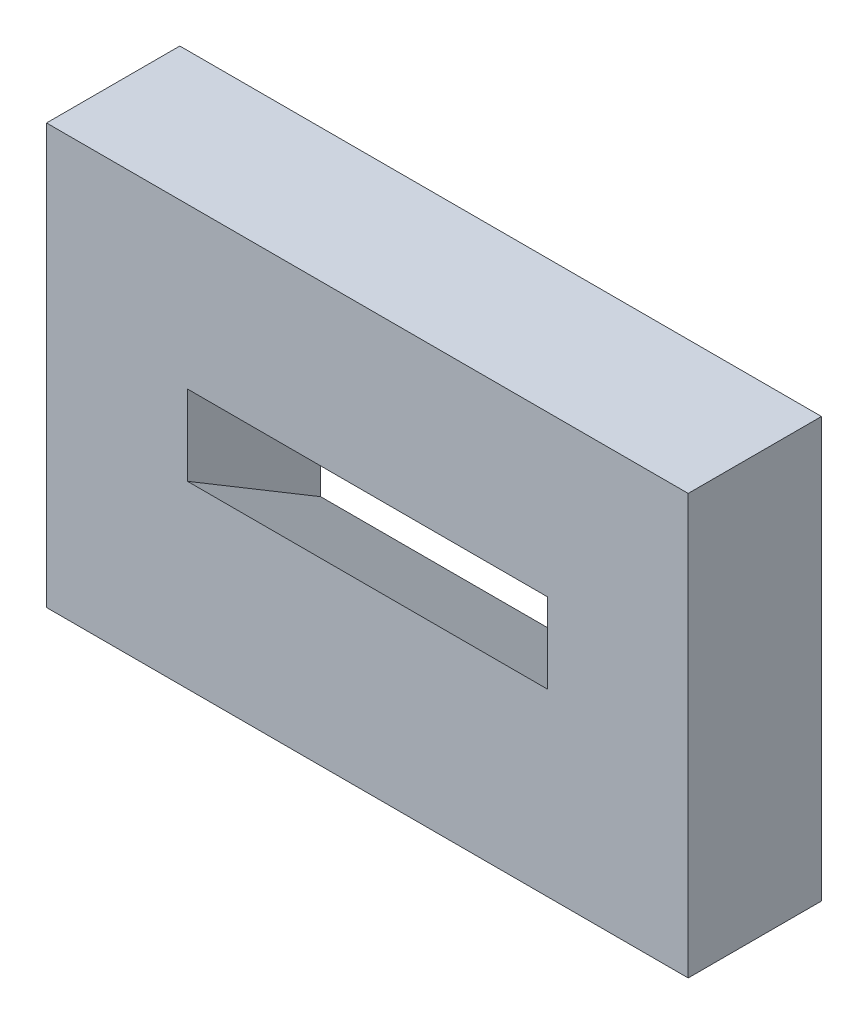
SolidWorks part; units mm, degrees
ref_plane "Ebene vorne" through (0, 0, 0) normal (0, 0, 1) x (1, 0, 0)
ref_plane "Ebene oben" through (0, 0, 0) normal (0, 1, 0) x (1, 0, 0)
ref_plane "Ebene rechts" through (0, 0, 0) normal (1, 0, 0) x (0, 0, -1)
sketch "Skizze1" plane through (0, 0, 0) normal (0, 0, 1) x (1, 0, 0)
  line L1 (-55, -85) -> (55, -85)
  line L2 (-55, -85) -> (-55, 85)
  line L3 (-55, 85) -> (55, 85)
  line L4 (55, -85) -> (55, 85)
  line L5 (-55, -85) -> (55, 85) construction
  line L6 (-55, 85) -> (55, -85) construction
  point P0 (0, 0)
  dimension "D1" = 110
  dimension "D2" = 170
extrude "Aufsatz-Linear austragen1" add sketch "Skizze1" along normal blind 5
sketch "Skizze2" plane through (0, 0, 5) normal (0, 0, 1) x (1, 0, 0)
  line L0 (-55, -85) -> (55, -85) construction
  line L1 (0, 85) -> (0, -85) construction
  line L2 (55, 85) -> (-55, 85) construction
  circle A1 centre (0, 0) radius 27
  dimension "D2" = 54
fillet "Verrundung1" radius 5 4 edges at (-55, -85, 2.5) (55, -85, 2.5) (55, 85, 2.5) (-55, 85, 2.5)
sketch "Skizze3" plane through (0, 0, 5) normal (0, 0, 1) x (1, 0, 0)
  line L0 (-35, 35) -> (-35, 17)
  line L1 (-35, -35) -> (35, -35) construction
  line L2 (-35, -35) -> (-35, 35) construction
  line L3 (-35, 35) -> (35, 35) construction
  line L4 (35, -35) -> (35, 35) construction
  line L5 (-35, -35) -> (35, 35) construction
  line L6 (-35, 35) -> (35, -35) construction
  line L7 (-35, 35) -> (-17, 35)
  line L8 (35, 35) -> (17, 35)
  line L9 (35, 35) -> (35, 17)
  line L10 (35, -35) -> (35, -17)
  line L11 (35, -35) -> (17, -35)
  line L12 (-35, -35) -> (-17, -35)
  line L13 (-35, -35) -> (-35, -17)
  arc A0 (-17, 35) -> (-35, 17) centre (0, 0) ccw
  arc A1 (35, 17) -> (17, 35) centre (0, 0) ccw
  arc A2 (17, -35) -> (35, -17) centre (0, 0) ccw
  arc A3 (-35, -17) -> (-17, -35) centre (0, 0) ccw
  point P0 (0, 0)
  point P21 (0, 0)
  dimension "D2" = 18
  dimension "D1" = 70
  dimension "D3" = 4
extrude "Schnitt-Linear austragen1" cut sketch "Skizze3" against normal through all
extrude "Schnitt-Linear austragen2" cut sketch "Skizze2" against normal blind 3
chamfer "Fase1" distance 3 angle 45 1 edges at (27, 0, 5)
sketch "Skizze4" plane through (0, 0, 0) normal (0, 0, -1) x (-1, 0, 0)
  line L0 (-50, 85) -> (50, 85) construction
  line L1 (-55, -80) -> (-55, 80) construction
  circle A0 centre (-49, 67) radius 4
  dimension "D1" = 18
  dimension "D3" = 8
  dimension "D2" = 6
extrude "Aufsatz-Linear austragen2" add sketch "Skizze4" along normal blind 69
chamfer "Fase2" distance 1 angle 45 1 edges at (45, 67, 0)
ref_plane "Ebene1" through (0, 0, -67) normal (0, 0, -1) x (-1, 0, 0)
sketch "Skizze5" plane through (0, 0, -67) normal (0, 0, -1) x (-1, 0, 0)
  circle A0 centre (-49, 67) radius 3
  circle A1 centre (-49, 67) radius 3.5
  dimension "D1" = 6
  dimension "D2" = 7
extrude "Schnitt-Linear austragen3" [suppressed] cut sketch "Skizze5" against normal blind 1
pattern_linear "Lineares Muster1" count 2 spacing 134 along (0, -1, 0) count 2 spacing 98 along (-1, 0, 0) of "Aufsatz-Linear austragen2", "Fase2"
fillet "Verrundung2" radius 1 12 edges at (-17, 35, 2.5) (-35, 35, 2.5) (-35, 17, 2.5) (-17, -35, 2.5) (-35, -17, 2.5) (-35, -35, 2.5) (35, -35, 2.5) (17, -35, 2.5) (35, -17, 2.5) (35, 17, 2.5) (35, 35, 2.5) (17, 35, 2.5)
thread "Gewinde1" pitch 1 method cut profile "Gewindeprofil1" start angle 0, offset 0, length 12, pitch 1, diameter 8
ref_plane "Ebene2" through (53, 67, -69) normal (0, -1, 0) x (1, 0, 0)
sketch "Gewindeprofil1" plane through (53, 67, -69) normal (0, -1, 0) x (1, 0, 0)
  line L0 (0, 0) -> (0, 1) construction
  line L11 (0, 0) -> (0, 0.875)
  line L12 (0, 0.875) -> (-0.5413, 0.5625)
  line L13 (-0.5413, 0.5625) -> (-0.5413, 0.3125)
  line L15 (-0.5413, 0.3125) -> (0, 0)
  line L17 (-0.5413, 0.4375) -> (0, 0.4375) construction
  point P2 (0, 0)
  dimension "Pitch" = 1
  dimension "Profile_Angle" = 60
  dimension "Profile_Land" = 0.25
  dimension "Profile_Height" = 0.5413
thread "Gewinde2" pitch 1 method cut profile "Gewindeprofil2" start angle 0, offset 0, length 12, pitch 1, diameter 8
ref_plane "Ebene3" through (53, -67, -69) normal (0, -1, 0) x (1, 0, 0)
sketch "Gewindeprofil2" plane through (53, -67, -69) normal (0, -1, 0) x (1, 0, 0)
  line L0 (0, 0) -> (0, 1) construction
  line L11 (0, 0) -> (0, 0.875)
  line L12 (0, 0.875) -> (-0.5413, 0.5625)
  line L13 (-0.5413, 0.5625) -> (-0.5413, 0.3125)
  line L15 (-0.5413, 0.3125) -> (0, 0)
  line L17 (-0.5413, 0.4375) -> (0, 0.4375) construction
  point P2 (0, 0)
  dimension "Pitch" = 1
  dimension "Profile_Angle" = 60
  dimension "Profile_Land" = 0.25
  dimension "Profile_Height" = 0.5413
thread "Gewinde3" pitch 1 method cut profile "Gewindeprofil3" start angle 0, offset 0, length 12, pitch 1, diameter 8
ref_plane "Ebene4" through (-45, -67, -69) normal (0, -1, 0) x (1, 0, 0)
sketch "Gewindeprofil3" plane through (-45, -67, -69) normal (0, -1, 0) x (1, 0, 0)
  line L0 (0, 0) -> (0, 1) construction
  line L11 (0, 0) -> (0, 0.875)
  line L12 (0, 0.875) -> (-0.5413, 0.5625)
  line L13 (-0.5413, 0.5625) -> (-0.5413, 0.3125)
  line L15 (-0.5413, 0.3125) -> (0, 0)
  line L17 (-0.5413, 0.4375) -> (0, 0.4375) construction
  point P2 (0, 0)
  dimension "Pitch" = 1
  dimension "Profile_Angle" = 60
  dimension "Profile_Land" = 0.25
  dimension "Profile_Height" = 0.5413
thread "Gewinde4" pitch 1 method cut profile "Gewindeprofil4" start angle 0, offset 0, length 12, pitch 1, diameter 8
ref_plane "Ebene5" through (-45, 67, -69) normal (0, -1, 0) x (1, 0, 0)
sketch "Gewindeprofil4" plane through (-45, 67, -69) normal (0, -1, 0) x (1, 0, 0)
  line L0 (0, 0) -> (0, 1) construction
  line L11 (0, 0) -> (0, 0.875)
  line L12 (0, 0.875) -> (-0.5413, 0.5625)
  line L13 (-0.5413, 0.5625) -> (-0.5413, 0.3125)
  line L15 (-0.5413, 0.3125) -> (0, 0)
  line L17 (-0.5413, 0.4375) -> (0, 0.4375) construction
  point P2 (0, 0)
  dimension "Pitch" = 1
  dimension "Profile_Angle" = 60
  dimension "Profile_Land" = 0.25
  dimension "Profile_Height" = 0.5413
sketch "Skizze10" plane through (0, 0, -69) normal (0, 0, -1) x (-1, 0, 0)
  line L0 (-49, 72) -> (-49, 62) construction
  line L2 (-60, -75) -> (60, -75)
  line L3 (-60, -75) -> (-60, 75)
  line L4 (-60, 75) -> (60, 75)
  line L5 (60, -75) -> (60, 75)
  line L6 (-60, -75) -> (60, 75) construction
  line L7 (-60, 75) -> (60, -75) construction
  circle A0 centre (-49, 67) radius 5 construction
  point P5 (0, 0)
  dimension "D1" = 150
  dimension "D2" = 120
extrude "Schnitt-Linear austragen4" cut sketch "Skizze10" against normal blind 2
sketch "Skizze12" plane through (0, 0, 0) normal (0, 0, -1) x (-1, 0, 0)
  line L0 (49, 67) -> (52.4587, 67) construction
  line L1 (49, 67) -> (45, 67) construction
  line L2 (49, 67) -> (49, 70.7835) construction
  line L3 (49, 67) -> (49, 63.4329) construction
  line L4 (0, 85) -> (0, -85) construction
  line L5 (-50, 85) -> (50, 85) construction
  line L6 (50, -85) -> (-50, -85) construction
  line L7 (-55, 0) -> (55, 0) construction
  line L8 (-55, -80) -> (-55, 80) construction
  line L9 (55, 80) -> (55, -80) construction
  arc A0 (50.3236, 63.8045) -> (52.1955, 68.3236) centre (49, 67) ccw construction
  circle A1 centre (49, 67) radius 4 construction
  circle A2 centre (49, 59.5) radius 2
  circle A3 centre (-49, 59.5) radius 2
  circle A4 centre (-49, -59.5) radius 2
  circle A5 centre (49, -59.5) radius 2
  spline S0 degree 3 poles (52.1955, 68.3236) (52.1009, 68.6178) (51.9696, 68.8928) (51.7191, 69.2775) (51.6259, 69.4018) (51.426, 69.6341) (51.3194, 69.7432) (50.98, 70.0501) (50.7243, 70.2287) (50.3196, 70.4416) (50.1806, 70.504) (49.8947, 70.6115) (49.7467, 70.6568) (49.2984, 70.7636) (48.9956, 70.7959) (48.5359, 70.7908) (48.3813, 70.7799) (48.0781, 70.7403) (47.9284, 70.7116) (47.4855, 70.5996) (47.1947, 70.4883) (46.6548, 70.2042) (46.4035, 70.0319) (46.1716, 69.8284) knots 0 0 0 0 0.125 0.125 0.1875 0.1875 0.25 0.25 0.375 0.375 0.4375 0.4375 0.5 0.5 0.625 0.625 0.6875 0.6875 0.75 0.75 0.875 0.875 1 1 1 1 construction
  spline S1 degree 3 poles (45, 67) (45.0201, 66.692) (45.076, 66.3926) (45.2569, 65.8101) (45.3838, 65.5256) (45.6176, 65.1334) (45.7031, 65.0075) (45.8892, 64.7654) (45.9906, 64.6485) (46.3125, 64.3192) (46.5492, 64.1283) (46.9396, 63.8878) (47.0766, 63.8148) (47.3557, 63.688) (47.6405, 63.5796) (47.9368, 63.5072) (48.239, 63.4533) (48.393, 63.4357) (48.8508, 63.4124) (49.1546, 63.4339) (49.7594, 63.5609) (50.0486, 63.6633) (50.3236, 63.8045) knots 0 0 0 0 0.125 0.125 0.25 0.25 0.3125 0.3125 0.375 0.375 0.5 0.5 0.5625 0.5625 0.625 0.6875 0.6875 0.75 0.75 0.875 0.875 1 1 1 1 construction
  dimension "D1" = 4
  dimension "D2" = 7.5
extrude "Schnitt-Linear austragen5" cut sketch "Skizze12" against normal blind 4.5
sketch "Skizze13" plane through (0, 0, 5) normal (0, 0, 1) x (1, 0, 0)
  line L0 (-50, -85) -> (50, -85) construction
  line L1 (-5.5, -77) -> (5.5, -77)
  line L2 (-5.5, -77) -> (-5.5, -74)
  line L3 (-5.5, -74) -> (5.5, -74)
  line L4 (5.5, -77) -> (5.5, -74)
  line L5 (-5.5, -77) -> (5.5, -74) construction
  line L6 (-5.5, -74) -> (5.5, -77) construction
  line L7 (0, 0) -> (0, -85) construction
  line L8 (0, 0) -> (0, 85) construction
  line L9 (44, -5.5) -> (47, -5.5)
  line L10 (44, -5.5) -> (44, 5.5)
  line L11 (44, 5.5) -> (47, 5.5)
  line L12 (47, -5.5) -> (47, 5.5)
  line L13 (44, -5.5) -> (47, 5.5) construction
  line L14 (44, 5.5) -> (47, -5.5) construction
  line L15 (50, 85) -> (-50, 85) construction
  line L16 (0, 0) -> (-55, 0) construction
  line L17 (-55, 80) -> (-55, -80) construction
  line L18 (0, 0) -> (55, 0) construction
  line L19 (55, -80) -> (55, 80) construction
  line L20 (-44, 5.5) -> (-47, 5.5)
  line L21 (-47, -5.5) -> (-47, 5.5)
  line L22 (-44, -5.5) -> (-47, -5.5)
  line L23 (-44, -5.5) -> (-44, 5.5)
  line L25 (-6.75, 76) -> (6.75, 76)
  line L26 (-6.75, 76) -> (-6.75, 79)
  line L27 (-6.75, 79) -> (6.75, 79)
  line L28 (6.75, 76) -> (6.75, 79)
  line L29 (-6.75, 76) -> (6.75, 79) construction
  line L30 (-6.75, 79) -> (6.75, 76) construction
  point P0 (0, -75.5)
  point P10 (45.5, 0)
  point P15 (0, 77.5)
  dimension "D1" = 3
  dimension "D2" = 11
  dimension "D3" = 8
  dimension "D4" = 8
  dimension "D5" = 13.5
  dimension "D6" = 3
  dimension "D7" = 6
extrude "Schnitt-Linear austragen6" cut sketch "Skizze13" against normal through all
sketch "Skizze14" plane through (0, 0, 5) normal (0, 0, 1) x (1, 0, 0)
  line L0 (-6.75, 76) -> (6.75, 76) construction
  line L1 (0, 85) -> (0, 76) construction
  line L2 (50, 85) -> (-50, 85) construction
  circle A0 centre (6, 65) radius 3
  circle A1 centre (-6, 65) radius 3
  dimension "D1" = 11
  dimension "D4" = 6
  dimension "D2" = 12
  dimension "D3" = 6
extrude "Aufsatz-Linear austragen3" add sketch "Skizze14" along normal blind 4
sketch "Skizze15" plane through (0, 0, 9) normal (0, 0, 1) x (1, 0, 0)
  circle A0 centre (-6, 65) radius 0.95
  circle A1 centre (6, 65) radius 0.95
  dimension "D1" = 1.9
extrude "Aufsatz-Linear austragen4" add sketch "Skizze15" along normal blind 4 draft 2
sketch "Skizze16" plane through (0, 0, 5) normal (0, 0, 1) x (1, 0, 0)
  line L1 (-60.7922, 59.1665) -> (62.8993, 59.1665)
  line L2 (-60.7922, 59.1665) -> (-60.7922, -89.6755)
  line L3 (-60.7922, -89.6755) -> (62.8993, -89.6755)
  line L4 (62.8993, 59.1665) -> (62.8993, -89.6755)
extrude "Schnitt-Linear austragen7" cut sketch "Skizze16" against normal through all
sketch "Skizze17" plane through (0, 0, 5) normal (0, 0, 1) x (1, 0, 0)
  line L0 (-6.75, 77.5) -> (6.75, 77.5) construction
  line L1 (-6.75, 79) -> (-6.75, 76) construction
  line L2 (6.75, 76) -> (6.75, 79) construction
  line L3 (0, 79) -> (0, 76) construction
  line L4 (-30.5, 76) -> (-19.5, 76)
  line L5 (-30.5, 76) -> (-30.5, 79)
  line L6 (-30.5, 79) -> (-19.5, 79)
  line L7 (-19.5, 76) -> (-19.5, 79)
  line L8 (-30.5, 76) -> (-19.5, 79) construction
  line L9 (-30.5, 79) -> (-19.5, 76) construction
  line L10 (6.75, 79) -> (-6.75, 79) construction
  line L11 (-6.75, 76) -> (6.75, 76) construction
  line L12 (30.5, 79) -> (19.5, 79)
  line L13 (19.5, 76) -> (19.5, 79)
  line L14 (30.5, 76) -> (19.5, 76)
  line L15 (30.5, 76) -> (30.5, 79)
  point P6 (-25, 77.5)
  point P17 (0, 0)
  point P18 (0, 0)
  point P19 (0, 77.5)
  dimension "D1" = 11
  dimension "D2" = 3
  dimension "D3" = 25
extrude "Schnitt-Linear austragen8" cut sketch "Skizze17" against normal through all
sketch "Skizze18" plane through (0, 0, 5) normal (0, 0, 1) x (1, 0, 0)
  line L0 (0, 85) -> (0, 59.1665) construction
  line L1 (-56.1297, 86.0363) -> (-31.9768, 86.0363)
  line L2 (-56.1297, 86.0363) -> (-56.1297, 52.475)
  line L3 (-56.1297, 52.475) -> (-31.9768, 52.475)
  line L4 (-31.9768, 86.0363) -> (-31.9768, 69.2557)
  line L5 (-31.9768, 69.2557) -> (-12.0365, 69.2557)
  line L7 (-31.9768, 52.475) -> (-12.0365, 52.475)
  line L8 (-12.0365, 69.2557) -> (-12.0365, 52.475)
  line L9 (50, 85) -> (-50, 85) construction
  line L10 (55, 59.1665) -> (-55, 59.1665) construction
  line L11 (56.1297, 86.0363) -> (56.1297, 52.475)
  line L12 (56.1297, 86.0363) -> (31.9768, 86.0363)
  line L13 (31.9768, 86.0363) -> (31.9768, 69.2557)
  line L14 (31.9768, 69.2557) -> (12.0365, 69.2557)
  line L15 (12.0365, 69.2557) -> (12.0365, 52.475)
  line L16 (31.9768, 52.475) -> (12.0365, 52.475)
  line L17 (56.1297, 52.475) -> (31.9768, 52.475)
extrude "Schnitt-Linear austragen9" cut sketch "Skizze18" against normal through all
sketch "Skizze19" plane through (0, 0, 5) normal (0, 0, 1) x (1, 0, 0)
  line L0 (-12.0365, 59.1665) -> (-12.0365, 69.2557) construction
  line L1 (-36.8635, 88.675) -> (-12.0365, 88.675)
  line L2 (-36.8635, 88.675) -> (-36.8635, 59.1665)
  line L3 (-36.8635, 59.1665) -> (-12.0365, 59.1665)
  line L4 (-12.0365, 88.675) -> (-12.0365, 69.2557)
  line L6 (12.0365, 59.1665) -> (35.4342, 59.1665)
  line L7 (12.0365, 69.2557) -> (12.0365, 91.605)
  line L8 (12.0365, 91.605) -> (35.4342, 91.605)
  line L9 (35.4342, 59.1665) -> (35.4342, 91.605)
  line L10 (-12.0365, 69.2557) -> (12.0365, 69.2557)
  line L12 (-12.0365, 59.1665) -> (12.0365, 59.1665)
extrude "Schnitt-Linear austragen10" cut sketch "Skizze19" against normal through all and the other way through all
chamfer "Fase3" distance 3 distance2 5 1 edges at (0, 76, 0) first distance on face at (0, 77.1278, 0)
